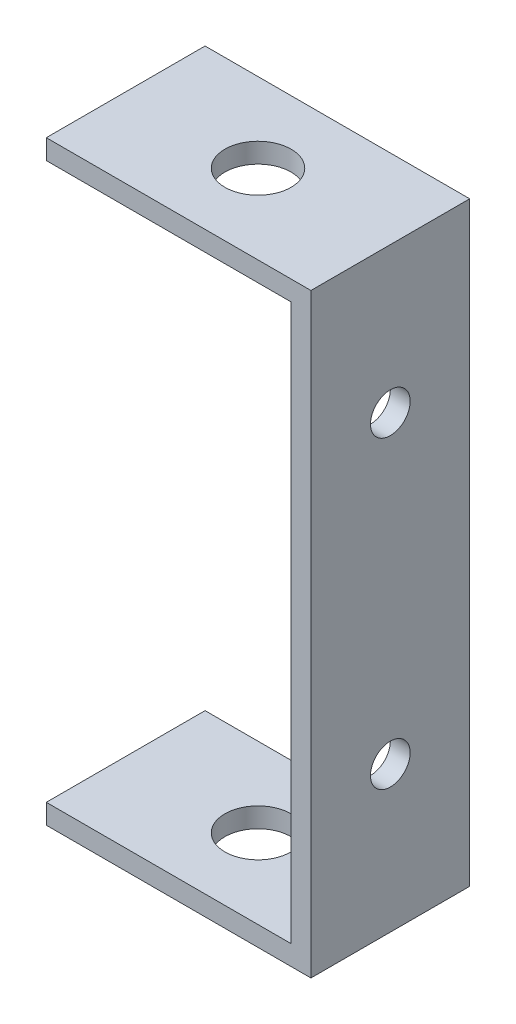
SolidWorks part; units mm, degrees
material "1060 Alloy"
ref_plane "Front Plane" through (0, 0, 0) normal (0, 0, 1) x (1, 0, 0)
ref_plane "Top Plane" through (0, 0, 0) normal (0, 1, 0) x (1, 0, 0)
ref_plane "Right Plane" through (0, 0, 0) normal (1, 0, 0) x (0, 0, -1)
sketch "Sketch1" plane through (0, 0, 0) normal (0, 1, 0) x (1, 0, 0)
  line L0 (8.5, 6) -> (8.5, -6)
  line L1 (-10, -6) -> (10, -6)
  line L2 (-10, -6) -> (-10, 6)
  line L3 (-10, 6) -> (10, 6)
  line L4 (10, -6) -> (10, 6)
  line L5 (-10, -6) -> (10, 6) construction
  line L6 (-10, 6) -> (10, -6) construction
  point P0 (0, 0)
  dimension "D1" = 20
  dimension "D2" = 12
  dimension "D3" = 1.5
extrude "Boss-Extrude1" add sketch "Sketch1" against normal blind 1.5 contours L3 L2 L1 L0 region at (-0.75, 0, 0)
extrude "Boss-Extrude2" add sketch "Sketch1<3>" against normal blind 45 contours L1 L4 L3 L0 region at (9.25, 0, 0)
sketch "Sketch1<3>" plane through (0, 0, 0) normal (0, 1, 0) x (1, 0, 0) same geometry as "Sketch1"
sketch "Sketch2" plane through (10, 0, 0) normal (1, 0, 0) x (0, 0, -1)
  line L0 (-6, 0) -> (6, 0) construction
  line L4 (7.8024, -22.5) -> (-3.7922, -22.5) construction
  line L5 (6, -45) -> (-6, -45) construction
  circle A0 centre (0, -34) radius 1.5
  circle A1 centre (0, -11) radius 1.5
  point P7 (0, 0)
  dimension "D1" = 3
  dimension "D2" = 22.5
  dimension "D3" = 23
extrude "Cut-Extrude1" cut sketch "Sketch2" against normal through all
extrude "Boss-Extrude3" add sketch "Sketch1<4>" along normal blind 1.5 from surface contours L3 L2 L1 L0 region at (-0.75, 0, 0) starting at face at (9.25, -45, 0)
sketch "Sketch1<4>" plane through (0, 0, 0) normal (0, 1, 0) x (1, 0, 0) same geometry as "Sketch1"
sketch "Sketch3" plane through (0, 0, 0) normal (0, 1, 0) x (1, 0, 0)
  line L0 (10, -6) -> (10, 6) construction
  circle A0 centre (0, 0) radius 2.5
  point P4 (0, 0)
  point P7 (0, -1.4282)
  point P9 (0, 0)
  dimension "D2" = 5
  dimension "D1" = 10
extrude "Cut-Extrude2" cut sketch "Sketch3" against normal through all
